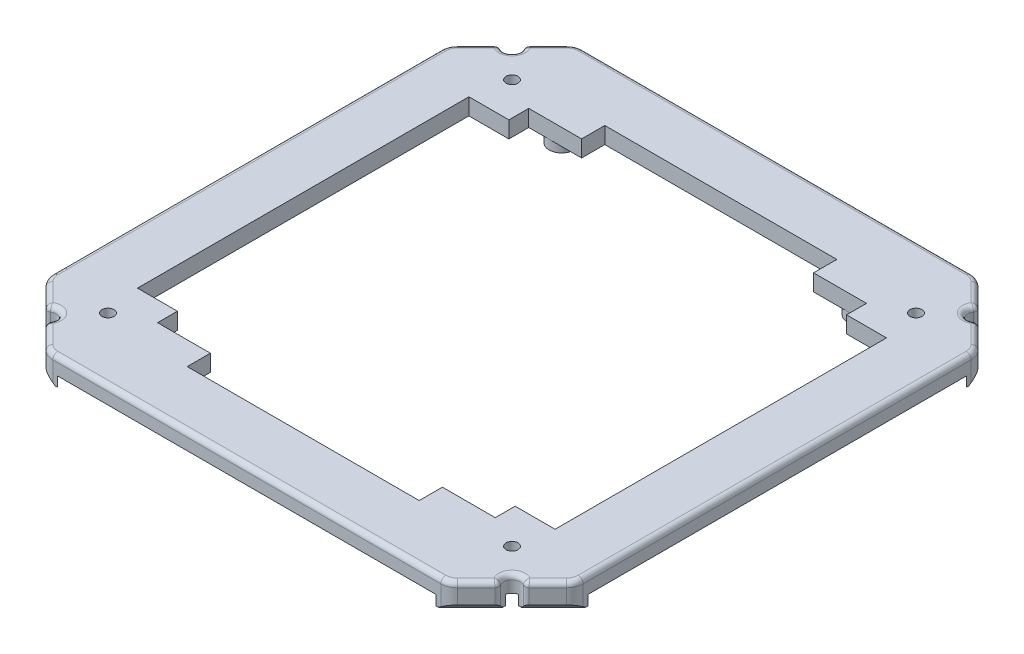
SolidWorks part; units mm, degrees
ref_plane "Front Plane" through (0, 0, 0) normal (0, 0, 1) x (1, 0, 0)
ref_plane "Top Plane" through (0, 0, 0) normal (0, 1, 0) x (1, 0, 0)
ref_plane "Right Plane" through (0, 0, 0) normal (1, 0, 0) x (0, 0, -1)
sketch "Sketch1" plane through (0, 0, 0) normal (0, 1, 0) x (1, 0, 0)
  line L0 (0, 0) -> (0, 25.4)
  line L1 (12.7, 38.1) -> (190.5, 38.1)
  line L2 (203.2, 25.4) -> (203.2, -152.4)
  line L3 (190.5, -165.1) -> (12.7, -165.1)
  line L4 (0, -152.4) -> (0, -127)
  line L5 (21.59, -127) -> (181.61, -127)
  line L6 (181.61, -127) -> (181.61, 0)
  line L7 (181.61, 0) -> (21.59, 0)
  line L10 (0, 0) -> (0, -127)
  line L12 (21.59, 0) -> (21.59, -127)
  arc A0 (12.7, -165.1) -> (0, -152.4) centre (12.7, -152.4) cw
  arc A1 (203.2, -152.4) -> (190.5, -165.1) centre (190.5, -152.4) cw
  arc A2 (190.5, 38.1) -> (203.2, 25.4) centre (190.5, 25.4) cw
  arc A3 (0, 25.4) -> (12.7, 38.1) centre (12.7, 25.4) cw
  point P13 (203.2, -165.1)
  point P16 (203.2, 38.1)
  point P19 (0, 38.1)
  dimension "D6" = 12.7
  dimension "D1" = 203.2
  dimension "D2" = 38.1
  dimension "D3" = 203.2
  dimension "D4" = 21.59
  dimension "D5" = 127
  dimension "D7" = 21.59
extrude "Boss-Extrude2" add sketch "Sketch1" along normal blind 6.35
sketch "Sketch2" plane through (0, 6.35, 0) normal (0, 1, 0) x (1, 0, 0)
  circle A0 centre (12.7, 25.4) radius 3.175
  circle A1 centre (190.5, 25.4) radius 3.175
  circle A2 centre (190.5, -152.4) radius 3.175
  circle A3 centre (12.7, -152.4) radius 3.175
  arc A4 (12.7, 38.1) -> (0, 25.4) centre (12.7, 25.4) ccw construction
  dimension "D1" = 6.35
extrude "Cut-Extrude1" cut sketch "Sketch2" against normal through all
sketch "Sketch8" plane through (0, 0, 0) normal (0, -1, 0) x (-1, 0, 0)
  line L0 (-3.7197, -161.3803) -> (-199.4803, 34.3803) construction
  line L1 (-24.1978, 13.9022) -> (-24.1978, 38.1) construction
  line L2 (-190.5, 38.1) -> (-12.7, 38.1) construction
  line L3 (-24.1978, 13.9022) -> (0, 13.9022) construction
  line L5 (-24.1978, 13.9022) -> (-3.7197, 34.3803) construction
  line L6 (0, 25.4) -> (0, -152.4) construction
  arc A0 (0, 25.4) -> (-12.7, 38.1) centre (-12.7, 25.4) ccw construction
  circle A1 centre (-24.1978, 13.9022) radius 2.286
  arc A2 (-12.7, -165.1) -> (0, -152.4) centre (-12.7, -152.4) ccw construction
  arc A3 (-190.5, 38.1) -> (-203.2, 25.4) centre (-190.5, 25.4) ccw construction
  circle A4 centre (-24.1978, -140.9022) radius 2.286
  circle A5 centre (-179.0022, -140.9022) radius 2.286
  circle A6 centre (-179.0022, 13.9022) radius 2.286
  point P8 (-101.6, -63.5)
  dimension "D2" = 4.572
  dimension "D1" = 28.9603
  dimension "D3" = 4
extrude "Cut-Extrude4" cut sketch "Sketch8" against normal through all
sketch "Sketch10" plane through (0, 0, 0) normal (0, -1, 0) x (-1, 0, 0)
  line L0 (-203.2, -152.4) -> (-203.2, 25.4) construction
  line L1 (-12.7, -165.1) -> (-190.5, -165.1) construction
  line L2 (-190.5, 38.1) -> (-12.7, 38.1) construction
  line L3 (0, 25.4) -> (0, -152.4) construction
  circle A0 centre (-44.45, -139.7) radius 2.286
  circle A1 centre (-158.75, -139.7) radius 2.286
  circle A2 centre (-158.75, 12.7) radius 2.286
  circle A3 centre (-44.45, 12.7) radius 2.286
  circle A4 centre (-44.45, 12.7) radius 4.826
  circle A5 centre (-158.75, 12.7) radius 4.826
  circle A6 centre (-158.75, -139.7) radius 4.826
  circle A7 centre (-44.45, -139.7) radius 4.826
  dimension "D1" = 4.572
  dimension "D2" = 44.45
  dimension "D3" = 25.4
  dimension "D4" = 25.4
  dimension "D5" = 44.45
  dimension "D6" = 2.54
extrude "Boss-Extrude3" add sketch "Sketch10" along normal blind 3.81
sketch "Sketch11" plane through (0, 0, 0) normal (0, -1, 0) x (1, 0, 0)
  line L0 (174.0713, -38.1) -> (187.3849, -24.7864)
  line L1 (190.5, -38.1) -> (12.7, -38.1) construction
  line L2 (203.2, 152.4) -> (203.2, -25.4) construction
  line L3 (203.2, -8.9713) -> (203.2, -13.4614)
  line L4 (203.2, -13.4614) -> (193.0933, -23.5682)
  line L5 (178.5614, -38.1) -> (174.0713, -38.1)
  line L6 (189.8864, -22.2849) -> (203.2, -8.9713)
  line L7 (188.6682, -27.9933) -> (178.5614, -38.1)
  line L8 (3.7197, -34.3803) -> (199.4803, 161.3803) construction
  line L9 (10.1067, -23.5682) -> (0, -13.4614)
  line L10 (0, -8.9713) -> (13.3136, -22.2849)
  line L11 (0, -13.4614) -> (0, -8.9713)
  line L12 (15.8151, -24.7864) -> (29.1287, -38.1)
  line L13 (24.6386, -38.1) -> (14.5318, -27.9933)
  line L14 (29.1287, -38.1) -> (24.6386, -38.1)
  line L15 (14.5318, 154.9933) -> (24.6386, 165.1)
  line L16 (29.1287, 165.1) -> (15.8151, 151.7864)
  line L17 (24.6386, 165.1) -> (29.1287, 165.1)
  line L18 (13.3136, 149.2849) -> (0, 135.9713)
  line L19 (0, 140.4614) -> (10.1067, 150.5682)
  line L20 (0, 135.9713) -> (0, 140.4614)
  line L21 (193.0933, 150.5682) -> (203.2, 140.4614)
  line L22 (203.2, 135.9713) -> (189.8864, 149.2849)
  line L23 (203.2, 140.4614) -> (203.2, 135.9713)
  line L24 (187.3849, 151.7864) -> (174.0713, 165.1)
  line L25 (178.5614, 165.1) -> (188.6682, 154.9933)
  line L26 (174.0713, 165.1) -> (178.5614, 165.1)
  arc A0 (187.3849, -24.7864) -> (188.6682, -27.9933) centre (190.5, -25.4) ccw
  arc A1 (193.0933, -23.5682) -> (189.8864, -22.2849) centre (190.5, -25.4) ccw
  arc A2 (0, -25.4) -> (12.7, -38.1) centre (12.7, -25.4) ccw construction
  arc A3 (203.2, 152.4) -> (190.5, 165.1) centre (190.5, 152.4) ccw construction
  arc A4 (13.3136, -22.2849) -> (10.1067, -23.5682) centre (12.7, -25.4) ccw
  arc A5 (14.5318, -27.9933) -> (15.8151, -24.7864) centre (12.7, -25.4) ccw
  arc A6 (15.8151, 151.7864) -> (14.5318, 154.9933) centre (12.7, 152.4) ccw
  arc A7 (10.1067, 150.5682) -> (13.3136, 149.2849) centre (12.7, 152.4) ccw
  arc A8 (189.8864, 149.2849) -> (193.0933, 150.5682) centre (190.5, 152.4) ccw
  arc A9 (188.6682, 154.9933) -> (187.3849, 151.7864) centre (190.5, 152.4) ccw
  point P22 (101.6, 63.5)
  dimension "D4" = 6.35
  dimension "D1" = 29.1287
  dimension "D2" = 29.1287
  dimension "D3" = 3.175
  dimension "D6" = 177.8
  dimension "D8" = 125.7236
  dimension "D5" = 4
extrude "Boss-Extrude4" add sketch "Sketch11" along normal blind 3.81
chamfer "Chamfer1" distance 2.54 angle 45 8 edges at (19.5852, -3.81, 160.0466) (5.0534, -3.81, 145.5148) (183.6148, -3.81, 160.0466) (198.1466, -3.81, 145.5148) (183.6148, -3.81, -33.0466) (198.1466, -3.81, -18.5148) (5.0534, -3.81, -18.5148) (19.5852, -3.81, -33.0466)
sketch "Sketch9" plane through (0, 6.35, 0) normal (0, 1, 0) x (1, 0, 0)
  line L0 (21.59, 0) -> (181.61, 0) construction
  line L1 (36.8978, 0) -> (166.3022, 0)
  line L2 (36.8978, 0) -> (36.8978, 7.62)
  line L3 (36.8978, 7.62) -> (57.15, 7.62)
  line L4 (166.3022, 0) -> (166.3022, 7.62)
  line L5 (181.61, -127) -> (21.59, -127) construction
  line L6 (166.3022, -127) -> (36.8978, -127)
  line L7 (166.3022, -127) -> (166.3022, -134.62)
  line L8 (166.3022, -134.62) -> (146.05, -134.62)
  line L9 (36.8978, -127) -> (36.8978, -134.62)
  line L11 (190.5, 38.1) -> (12.7, 38.1) construction
  line L14 (57.15, -134.62) -> (57.15, -143.51)
  line L15 (57.15, -143.51) -> (146.05, -143.51)
  line L16 (146.05, -134.62) -> (146.05, -143.51)
  line L18 (57.15, 7.62) -> (57.15, 16.51)
  line L19 (57.15, 16.51) -> (146.05, 16.51)
  line L20 (146.05, 7.62) -> (146.05, 16.51)
  line L21 (174.0713, 38.1) -> (29.1287, 38.1) construction
  line L22 (57.15, -134.62) -> (36.8978, -134.62)
  line L23 (146.05, 7.62) -> (166.3022, 7.62)
  circle A0 centre (179.0022, 13.9022) radius 2.286 construction
  circle A1 centre (24.1978, 13.9022) radius 2.286 construction
  circle A2 centre (44.45, 12.7) radius 2.286 construction
  point P30 (101.6, 16.51)
  point P31 (101.6, -127)
  point P32 (101.6, -143.51)
  dimension "D4" = 12.7
  dimension "D1" = 12.7
  dimension "D2" = 12.7
  dimension "D3" = 30.48
  dimension "D5" = 21.59
extrude "Cut-Extrude5" cut sketch "Sketch9" against normal through all
sketch "Sketch13" plane through (0, 0, 0) normal (0, -1, 0) x (1, 0, 0)
  line L0 (57.15, -7.62) -> (36.8978, -7.62) construction
  line L1 (54.61, -12.7) -> (74.295, -12.7)
  line L2 (54.61, -12.7) -> (54.61, -26.775)
  line L3 (54.61, -33.02) -> (74.295, -33.02)
  line L4 (148.59, -12.7) -> (148.59, -26.775)
  line L5 (174.0713, -38.1) -> (29.1287, -38.1) construction
  line L6 (99.06, -12.7) -> (79.375, -26.775)
  line L8 (99.06, -18.945) -> (99.06, -33.02)
  line L10 (104.14, -18.945) -> (104.14, -33.02)
  line L12 (123.825, -12.7) -> (123.825, -26.775)
  line L14 (128.905, -18.945) -> (128.905, -33.02)
  line L16 (74.295, -18.945) -> (74.295, -33.02)
  line L18 (79.375, -12.7) -> (79.375, -26.775)
  line L19 (128.905, -33.02) -> (148.59, -33.02)
  line L20 (79.375, -33.02) -> (99.06, -18.945)
  line L21 (128.905, -12.7) -> (148.59, -12.7)
  line L22 (104.14, -12.7) -> (123.825, -26.775)
  line L23 (104.14, -12.7) -> (123.825, -12.7)
  line L24 (104.14, -18.945) -> (123.825, -33.02)
  line L25 (128.905, -12.7) -> (148.59, -26.775)
  line L26 (-818.39, 63.5) -> (49181.61, 63.5) construction
  line L27 (148.59, -33.02) -> (128.905, -18.945)
  line L28 (104.14, -33.02) -> (123.825, -33.02)
  line L29 (74.295, -12.7) -> (54.61, -26.775)
  line L31 (54.61, -33.02) -> (74.295, -18.945)
  line L32 (79.375, -33.02) -> (99.06, -33.02)
  line L33 (79.375, -12.7) -> (99.06, -12.7)
  line L34 (181.61, 127) -> (181.61, 0) construction
  line L35 (79.375, 139.7) -> (99.06, 139.7)
  line L36 (79.375, 160.02) -> (99.06, 160.02)
  line L37 (54.61, 160.02) -> (74.295, 145.945)
  line L38 (74.295, 139.7) -> (54.61, 153.775)
  line L39 (104.14, 160.02) -> (123.825, 160.02)
  line L40 (148.59, 160.02) -> (128.905, 145.945)
  line L41 (128.905, 139.7) -> (148.59, 153.775)
  line L42 (104.14, 145.945) -> (123.825, 160.02)
  line L43 (104.14, 139.7) -> (123.825, 139.7)
  line L44 (104.14, 139.7) -> (123.825, 153.775)
  line L45 (128.905, 139.7) -> (148.59, 139.7)
  line L46 (79.375, 160.02) -> (99.06, 145.945)
  line L47 (128.905, 160.02) -> (148.59, 160.02)
  line L48 (79.375, 139.7) -> (79.375, 153.775)
  line L49 (74.295, 145.945) -> (74.295, 160.02)
  line L50 (128.905, 145.945) -> (128.905, 160.02)
  line L51 (123.825, 139.7) -> (123.825, 153.775)
  line L52 (104.14, 145.945) -> (104.14, 160.02)
  line L53 (99.06, 145.945) -> (99.06, 160.02)
  line L54 (99.06, 139.7) -> (79.375, 153.775)
  line L55 (148.59, 139.7) -> (148.59, 153.775)
  line L56 (54.61, 160.02) -> (74.295, 160.02)
  line L57 (54.61, 139.7) -> (54.61, 153.775)
  line L58 (54.61, 139.7) -> (74.295, 139.7)
  circle A0 centre (44.45, -12.7) radius 2.286 construction
  circle A1 centre (158.75, -12.7) radius 2.286 construction
  point P50 (181.61, 63.5)
  dimension "D1" = 5.08
  dimension "D2" = 5.08
  dimension "D3" = 10.16
  dimension "D4" = 10.16
  dimension "D5" = 5.08
  dimension "D6" = 5.08
  dimension "D7" = 5.08
  dimension "D8" = 5.08
  dimension "D9" = 5.08
  dimension "D10" = 5.08
  dimension "D11" = 5.08
  dimension "D12" = 93.98
sketch "Sketch14" plane through (0, 0, 0) normal (0, -1, 0) x (1, 0, 0)
  line L0 (12.7, -38.1) -> (24.6386, -38.1) construction
  line L1 (24.6386, -38.1) -> (14.5318, -27.9933) construction
  line L2 (10.1067, -23.5682) -> (0, -13.4614) construction
  line L3 (0, -13.4614) -> (0, -25.4) construction
  line L4 (203.2, -25.4) -> (203.2, -13.4614) construction
  line L5 (203.2, -13.4614) -> (193.0933, -23.5682) construction
  line L6 (188.6682, -27.9933) -> (178.5614, -38.1) construction
  line L7 (178.5614, -38.1) -> (190.5, -38.1) construction
  line L8 (190.5, 165.1) -> (178.5614, 165.1) construction
  line L9 (178.5614, 165.1) -> (188.6682, 154.9933) construction
  line L10 (193.0933, 150.5682) -> (203.2, 140.4614) construction
  line L11 (203.2, 140.4614) -> (203.2, 152.4) construction
  line L12 (12.7, -38.1) -> (24.6386, -38.1)
  line L13 (24.6386, -38.1) -> (14.5318, -27.9933)
  line L14 (10.1067, -23.5682) -> (0, -13.4614)
  line L15 (0, -13.4614) -> (0, -25.4)
  line L16 (203.2, -25.4) -> (203.2, -13.4614)
  line L17 (203.2, -13.4614) -> (193.0933, -23.5682)
  line L18 (188.6682, -27.9933) -> (178.5614, -38.1)
  line L19 (178.5614, -38.1) -> (190.5, -38.1)
  line L20 (190.5, 165.1) -> (178.5614, 165.1)
  line L21 (178.5614, 165.1) -> (188.6682, 154.9933)
  line L22 (193.0933, 150.5682) -> (203.2, 140.4614)
  line L23 (203.2, 140.4614) -> (203.2, 152.4)
  line L40 (0, 152.4) -> (0, 140.4614)
  line L41 (0, 140.4614) -> (10.1067, 150.5682)
  line L42 (14.5318, 154.9933) -> (24.6386, 165.1)
  line L43 (24.6386, 165.1) -> (12.7, 165.1)
  line L44 (0, 152.4) -> (0, 140.4614)
  line L45 (0, 140.4614) -> (10.1067, 150.5682)
  line L46 (14.5318, 154.9933) -> (24.6386, 165.1)
  line L47 (24.6386, 165.1) -> (12.7, 165.1)
  arc A0 (10.1067, -23.5682) -> (14.5318, -27.9933) centre (12.7, -25.4) ccw construction
  arc A1 (0, -25.4) -> (12.7, -38.1) centre (12.7, -25.4) ccw construction
  arc A2 (188.6682, -27.9933) -> (193.0933, -23.5682) centre (190.5, -25.4) ccw construction
  arc A3 (190.5, -38.1) -> (203.2, -25.4) centre (190.5, -25.4) ccw construction
  arc A4 (193.0933, 150.5682) -> (188.6682, 154.9933) centre (190.5, 152.4) ccw construction
  arc A5 (203.2, 152.4) -> (190.5, 165.1) centre (190.5, 152.4) ccw construction
  arc A6 (10.1067, -23.5682) -> (14.5318, -27.9933) centre (12.7, -25.4) ccw
  arc A7 (0, -25.4) -> (12.7, -38.1) centre (12.7, -25.4) ccw
  arc A12 (188.6682, -27.9933) -> (193.0933, -23.5682) centre (190.5, -25.4) ccw
  arc A13 (190.5, -38.1) -> (203.2, -25.4) centre (190.5, -25.4) ccw
  arc A14 (193.0933, 150.5682) -> (188.6682, 154.9933) centre (190.5, 152.4) ccw
  arc A15 (203.2, 152.4) -> (190.5, 165.1) centre (190.5, 152.4) ccw
  arc A18 (14.5318, 154.9933) -> (10.1067, 150.5682) centre (12.7, 152.4) ccw
  arc A19 (12.7, 165.1) -> (0, 152.4) centre (12.7, 152.4) ccw
  arc A20 (14.5318, 154.9933) -> (10.1067, 150.5682) centre (12.7, 152.4) ccw
  arc A21 (12.7, 165.1) -> (0, 152.4) centre (12.7, 152.4) ccw
  dimension "D1" = 0
extrude "Cut-Extrude6" cut sketch "Sketch14" against normal up to next
fillet "Fillet1" radius 6.35 8 edges at (24.6386, 2.54, 165.1) (0, 2.54, 140.4614) (0, 2.54, -13.4614) (24.6386, 2.54, -38.1) (178.5614, 2.54, -38.1) (203.2, 2.54, -13.4614) (203.2, 2.54, 140.4614) (178.5614, 2.54, 165.1)
fillet "Fillet2" radius 1.5875 8 edges at (14.5318, 2.54, -27.9933) (10.1067, 2.54, -23.5682) (188.6682, 2.54, -27.9933) (193.0933, 2.54, -23.5682) (193.0933, 2.54, 150.5682) (188.6682, 2.54, 154.9933) (10.1067, 2.54, 150.5682) (14.5318, 2.54, 154.9933)
fillet "Fillet3" radius 1.905 32 edges at (9.981, 6.35, 149.951) (14.9451, 6.35, 150.1549) (15.149, 6.35, 155.119) (19.1914, 6.35, 159.6529) (24.8388, 6.35, 164.6166) (101.6, 6.35, 165.1) (178.3612, 6.35, 164.6166) (184.0086, 6.35, 159.6529) (188.051, 6.35, 155.119) (188.2549, 6.35, 150.1549) (193.219, 6.35, 149.951) (197.7529, 6.35, 145.9086) (202.7166, 6.35, 140.2612) (203.2, 6.35, 63.5) (202.7166, 6.35, -13.2612) (197.7529, 6.35, -18.9086) (193.219, 6.35, -22.951) (188.2549, 6.35, -23.1549) (188.051, 6.35, -28.119) (184.0086, 6.35, -32.6529) (178.3612, 6.35, -37.6166) (101.6, 6.35, -38.1) (24.8388, 6.35, -37.6166) (19.1914, 6.35, -32.6529) (15.149, 6.35, -28.119) (14.9451, 6.35, -23.1549) (9.981, 6.35, -22.951) (5.4471, 6.35, -18.9086) (0.4834, 6.35, -13.2612) (0, 6.35, 63.5) (0.4834, 6.35, 140.2612) (5.4471, 6.35, 145.9086)
